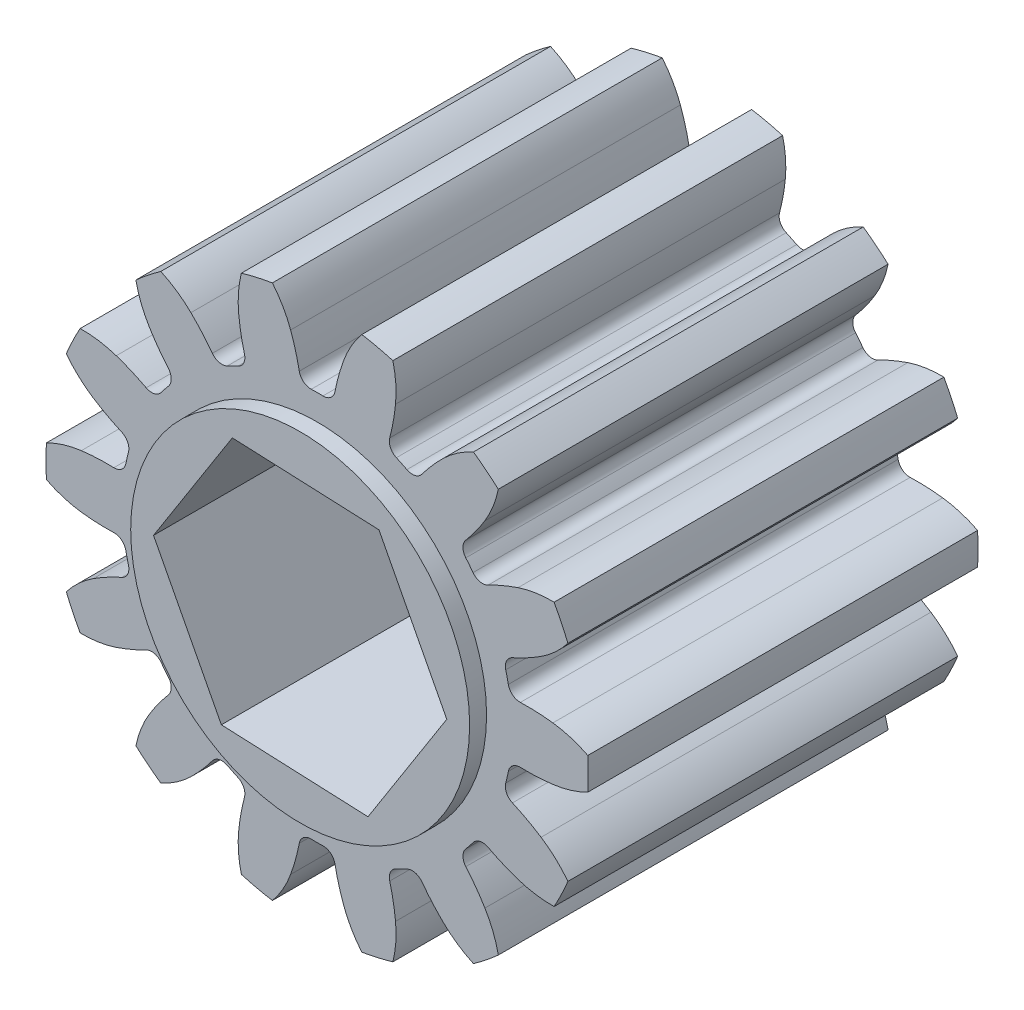
SolidWorks part; units mm, degrees
material "Plain Carbon Steel"
ref_plane "Front" through (0, 0, 0) normal (0, 0, 1) x (1, 0, 0)
ref_plane "Top" through (0, 0, 0) normal (0, 1, 0) x (1, 0, 0)
ref_plane "Right" through (0, 0, 0) normal (1, 0, 0) x (0, 0, -1)
sketch "Sketch1" plane through (0, 0, 0) normal (0, 0, 1) x (1, 0, 0)
  line L0 (0, 0) -> (8.89, 0) construction
  line L1 (8.89, 0) -> (10.16, 0) construction
  circle A0 centre (0, 0) radius 8.89 construction
  circle A1 centre (0, 0) radius 10.16
  dimension "pitch_diameter" = 17.78
  dimension "addendum" = 1.27
extrude "BLANK DISK" add sketch "Sketch1" along normal mid plane 14.605
sketch "Sketch2" plane through (0, 0, 7.3025) normal (0, 0, 1) x (1, 0, 0)
  line L0 (0, 0) -> (7.3025, 0) construction
  line L1 (7.3025, 0) -> (8.89, 0) construction
  line L2 (0, 0) -> (-10.16, 0) construction
  line L3 (0, 0) -> (-9.1538, -4.4083) construction
  line L4 (-9.3967, -3.8636) -> (-8.3919, -2.9341) construction
  line L5 (-8.3919, -2.9341) -> (-6.9724, -2.1707) construction
  line L6 (-10.1425, -0.5961) -> (-8.8339, -0.9976) construction
  line L7 (-8.8339, -0.9976) -> (-7.2238, -1.0695) construction
  line L8 (-7.959, -3.8329) -> (-8.3919, -2.9341) construction
  line L9 (-8.8339, -0.9976) -> (-8.8339, 0) construction
  line L12 (0, 0) -> (-8.8339, -0.9976) construction
  line L13 (0, 0) -> (-8.3919, -2.9341) construction
  line L14 (-8.3919, -2.9341) -> (-6.7685, -7.5771) construction
  line L15 (-8.8339, -0.9976) -> (-9.3858, 3.89) construction
  line L16 (-8.3919, -2.9341) -> (-8.8339, -0.9976) construction
  line L17 (-7.1194, -1.625) -> (-7.2238, -1.0695) construction
  line L18 (-7.1194, -1.625) -> (-6.9724, -2.1707) construction
  circle A0 centre (0, 0) radius 8.89 construction
  circle A1 centre (0, 0) radius 7.3025 construction
  circle A2 centre (0, 0) radius 10.16 construction
  arc A3 (-9.3967, -3.8636) -> (-10.1425, -0.5961) centre (0, 0) cw
  arc A4 (-6.9724, -2.1707) -> (-7.2238, -1.0695) centre (0, 0) cw construction
  arc A6 (-9.3967, -3.8636) -> (-8.3919, -2.9341) centre (-6.2247, -6.2846) cw
  arc A7 (-10.1425, -0.5961) -> (-8.8339, -0.9976) centre (-8.3351, 2.9615) ccw
  arc A8 (-8.3919, -2.9341) -> (-7.3187, -2.3554) centre (-4.227, -9.3733) cw
  arc A9 (-8.8339, -0.9976) -> (-7.6159, -1.0533) centre (-7.8753, 6.611) ccw
  arc A10 (-7.3187, -2.3554) -> (-7.0677, -1.8368) centre (-7.4979, -1.9486) ccw
  arc A11 (-7.6159, -1.0533) -> (-7.1648, -1.4117) centre (-7.6009, -1.4976) cw
  arc A12 (-7.0677, -1.8368) -> (-7.1648, -1.4117) centre (0, 0) cw
  dimension "D12" = 3.9903
  dimension "D3" = 25.714
  dimension "D4" = 0.9976
  dimension "D5" = 0.9976
  dimension "D11" = 1.9863
  dimension "D14" = 9
  dimension "D15" = 9
  dimension "base_fillet" = 0.4445
  dimension "pitch_diameter" = 17.78
  dimension "deddendum" = 1.5875
extrude "GEAR TOOTH CUT" cut sketch "Sketch2" against normal through all
ref_axis "CENTER AXIS" through (0, 0, 50) along (0, 0, -1)
pattern_circular "GEAR TEETH REVOLVE" count 14 over 360 about axis through (0, 0, 50) along (0, 0, -1) of "GEAR TOOTH CUT"
sketch "Sketch4" plane through (0, 0, 7.3025) normal (0, 0, 1) x (1, 0, 0)
  circle A0 centre (0, 0) radius 6.35
  dimension "D1" = 12.7
extrude "Extrude1" add sketch "Sketch4" along normal blind 0.635
sketch "Sketch3" plane through (0, 0, 7.3025) normal (0, 0, 1) x (1, 0, 0)
  line L1 (2.9524, 4.6395) -> (-2.5417, 4.8766)
  line L2 (-2.5417, 4.8766) -> (-5.4941, 0.2371)
  line L3 (-5.4941, 0.2371) -> (-2.9524, -4.6395)
  line L4 (-2.9524, -4.6395) -> (2.5417, -4.8766)
  line L5 (2.5417, -4.8766) -> (5.4941, -0.2371)
  line L6 (5.4941, -0.2371) -> (2.9524, 4.6395)
  circle A0 centre (0, 0) radius 4.7625 construction
  dimension "HEX_SIZE" = 9.525
extrude "HEX BORE CUT" cut sketch "Sketch3" against normal through all and the other way through all
equation "\"N_teeth\" = 14.000000"
equation "\"pitch_diameter\" = .7000000"
equation "\"Pd\"=\"N_teeth\"/\"pitch_diameter\""
equation "\"addendum\"=1.000/\"Pd\""
equation "\"face_width\"=0.575000"
equation "\"deddendum\"=1.250/\"Pd\""
equation "\"D3@Sketch2\" = 360/\"N_teeth\""
equation "\"tooth_thickness\"=1.571/\"Pd\""
equation "\"D4@Sketch2\" = \"tooth_thickness\"/2"
equation "\"D5@Sketch2\" = \"tooth_thickness\"/2"
equation "\"Pressure_Angle\"=14.500000"
equation "\"base_fillet\"=0.35/\"Pd\""
equation "\"D12@Sketch2\" = 2*\"tooth_thickness\""
equation "\"hub_diameter\"=0.500000"
equation "\"bore\"=0.375000"
equation "\"hub_projection\"=0.250000"
equation "\"sss_diam\"=0.062500"
